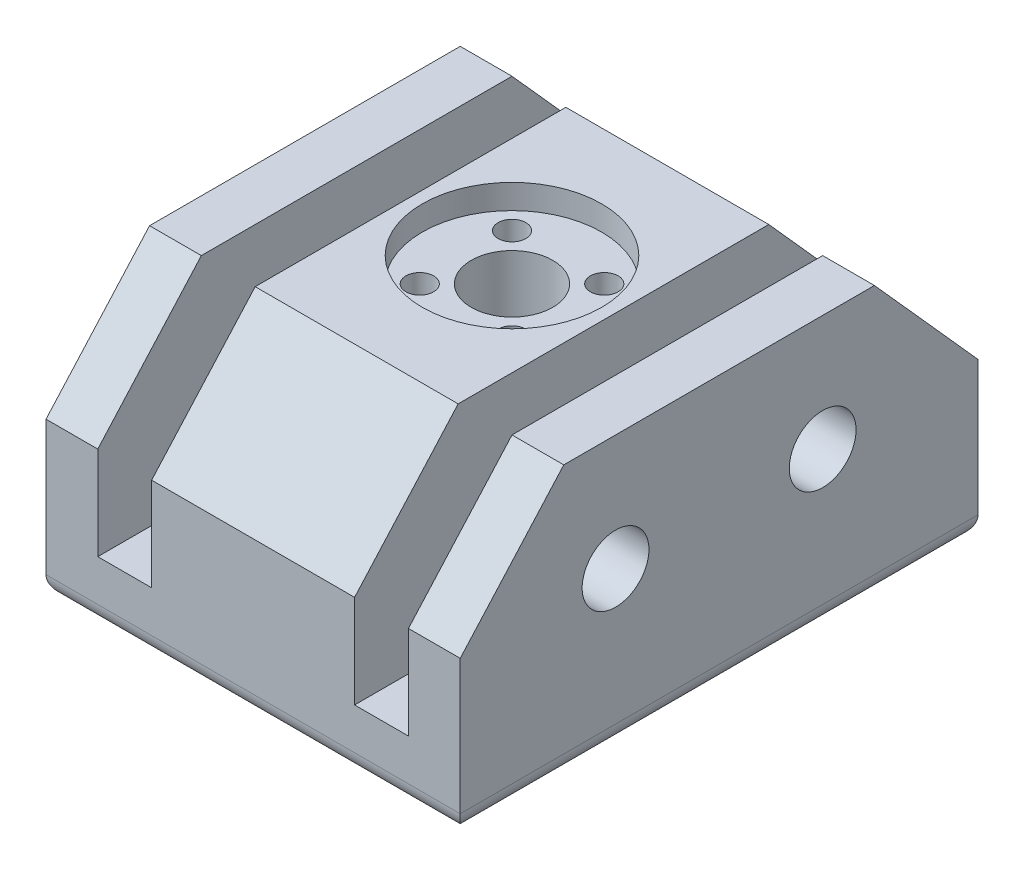
SolidWorks part; units mm, degrees
ref_plane "Front Plane" through (0, 0, 0) normal (0, 0, 1) x (1, 0, 0)
ref_plane "Top Plane" through (0, 0, 0) normal (0, 1, 0) x (1, 0, 0)
ref_plane "Right Plane" through (0, 0, 0) normal (1, 0, 0) x (0, 0, -1)
sketch "Sketch1" plane through (0, 0, 0) normal (1, 0, 0) x (0, 0, -1)
  line L1 (0, 0) -> (63.5, 0)
  line L2 (0, 0) -> (0, 6.35)
  line L3 (0, 6.35) -> (63.5, 6.35)
  line L4 (63.5, 0) -> (63.5, 6.35)
  dimension "D1" = 6.35
  dimension "D2" = 63.5
extrude "Boss-Extrude1" add sketch "Sketch1" against normal blind 50.8
sketch "Sketch2" plane through (0, 0, 0) normal (1, 0, 0) x (0, 0, -1)
  line L0 (0, 6.35) -> (0, 19.05)
  line L1 (0, 19.05) -> (12.7, 33.249)
  line L2 (12.7, 33.249) -> (50.8, 33.249)
  line L3 (50.8, 33.249) -> (63.5, 19.05)
  line L4 (63.5, 19.05) -> (63.5, 6.35)
  line L5 (63.5, 6.35) -> (0, 6.35)
  point P7 (31.75, 33.249)
  point P10 (31.75, 6.35)
  dimension "D1" = 38.1
  dimension "D2" = 12.7
  dimension "D3" = 12.7
  dimension "D4" = 19.05
  dimension "D5" = 19.05
extrude "Boss-Extrude2" add sketch "Sketch2" against normal blind 50.8
sketch "Sketch10" plane through (0, 0, -63.5) normal (0, 0, -1) x (-1, 0, 0)
  line L1 (50.8, 33.249) -> (0, 33.249) construction
  line L3 (6.35, 7.62) -> (6.35, 33.249)
  line L4 (6.35, 33.249) -> (12.954, 33.249)
  line L5 (12.954, 7.62) -> (12.954, 33.249)
  line L6 (6.35, 7.62) -> (12.954, 7.62)
  line L8 (50.8, 0) -> (0, 0) construction
  point P11 (12.954, 7.62)
  dimension "D1" = 7.62
  dimension "D2" = 6.604
  dimension "D3" = 6.35
extrude "Cut-Extrude1" cut sketch "Sketch10" against normal through all
pattern_linear "LPattern3" count 2 spacing 31.496 along (-1, 0, 0) of "Cut-Extrude1"
sketch "Sketch11" plane through (0, 0, 0) normal (1, 0, 0) x (0, 0, -1)
  circle A0 centre (19.05, 19.05) radius 4.0957
  circle A1 centre (19.05, 19.05) radius 7.9375 construction
  circle A2 centre (44.45, 19.05) radius 4.0958
  circle A3 centre (44.45, 19.05) radius 7.9375 construction
  dimension "D1" = 8.1915
  dimension "D3" = 15.875
  dimension "D4" = 8.1915
  dimension "D6" = 15.875
  dimension "D2" = 6.35
  dimension "D5" = 6.35
extrude "Cut-Extrude2" cut sketch "Sketch11" against normal through all
sketch "Sketch14" plane through (0, 33.249, 0) normal (0, 1, 0) x (1, 0, 0)
  line L3 (-37.846, 12.7) -> (-37.846, 50.8) construction
  point P0 (-25.4, 31.75)
  point P4 (-37.846, 31.75)
  dimension "D1" = 12.446
sketch "Sketch17" plane through (0, 40.0201, -44.7438) normal (0, 0.6667, -0.7454) x (-1, 0, 0)
  line L0 (12.954, -28.1343) -> (12.954, -9.0843) construction
  line L1 (37.846, -9.0843) -> (12.954, -9.0843) construction
  point P0 (25.4, -18.6093)
  point P4 (12.954, -18.6093)
  point P7 (25.4, -9.0843)
sketch "Sketch18" plane through (0, 8.4667, 9.466) normal (0, 0.6667, 0.7454) x (1, 0, 0)
  line L0 (-12.954, 33.249) -> (-12.954, 14.199) construction
  line L1 (-37.846, 33.249) -> (-12.954, 33.249) construction
  point P0 (-25.4, 23.724)
  point P1 (-25.4, 23.724)
  point P4 (-12.954, 23.724)
  point P7 (-25.4, 33.249)
ref_plane "Plane2" through (0, 33.02, 0) normal (0, -1, 0) x (-1, 0, 0)
fillet "Fillet1" radius 2.54 4 edges at (0, 0, -31.75) (-50.8, 0, -31.75) (-25.4, 0, 0) (-25.4, 0, -63.5)
sketch "Sketch21" plane through (0, 0, 0) normal (0, -1, 0) x (1, 0, 0)
  line L0 (-25.4, -63.5) -> (-25.4, 0) construction
  line L1 (-50.8, -63.5) -> (0, -63.5) construction
  line L2 (-50.8, 0) -> (0, 0) construction
  line L3 (-50.8, -31.75) -> (0, -31.75) construction
  line L4 (-50.8, 0) -> (-50.8, -63.5) construction
  line L5 (0, 0) -> (0, -63.5) construction
  circle A0 centre (-31.0569, -37.4069) radius 1.7
  circle A1 centre (-31.0569, -26.0931) radius 1.7
  circle A2 centre (-19.7431, -26.0931) radius 1.7
  circle A3 centre (-19.7431, -37.4069) radius 1.7
  point P14 (-25.4, -31.75)
  point P24 (-25.4, -31.75)
  dimension "D1" = 3.4
  dimension "D2" = 8
  dimension "D4" = 4
sketch "Sketch22" plane through (0, 33.249, 0) normal (0, -1, 0) x (1, 0, 0)
  line L1 (-25.4, -63.5) -> (-25.4, 0) construction
  line L2 (-50.8, -63.5) -> (0, -63.5) construction
  line L3 (-50.8, 0) -> (0, 0) construction
  line L4 (0, -31.75) -> (-50.8, -31.75) construction
  line L6 (0, 0) -> (0, -63.5) construction
  line L7 (-50.8, 0) -> (-50.8, -63.5) construction
  circle A1 centre (-25.4, -31.75) radius 11
  dimension "D1" = 22
extrude "Cut-Extrude7" cut sketch "Sketch21" against normal up to next
extrude "Cut-Extrude8" cut sketch "Sketch22" along normal blind 3
sketch "Sketch24" plane through (0, 0, 0) normal (0, -1, 0) x (1, 0, 0)
  line L0 (-25.4, -63.5) -> (-25.4, 0) construction
  line L1 (-50.8, -63.5) -> (0, -63.5) construction
  line L2 (-50.8, 0) -> (0, 0) construction
  line L3 (0, -31.75) -> (-50.8, -31.75) construction
  line L4 (0, 0) -> (0, -63.5) construction
  line L5 (-50.8, 0) -> (-50.8, -63.5) construction
  circle A0 centre (-25.4, -31.75) radius 5
  dimension "D1" = 10
extrude "Cut-Extrude10" cut sketch "Sketch24" against normal through all
sketch "Sketch28" plane through (0, 0, 0) normal (0, -1, 0) x (1, 0, 0)
  circle A0 centre (-19.7431, -37.4069) radius 3.125
  circle A1 centre (-25.4, -31.75) radius 8 construction
  circle A2 centre (-31.0569, -37.4069) radius 3.125
  circle A3 centre (-31.0569, -26.0931) radius 3.125
  circle A4 centre (-19.7431, -26.0931) radius 3.125
  point P16 (-25.4, -31.75)
  dimension "D1" = 6.25
  dimension "D2" = 4
extrude "Cut-Extrude11" cut sketch "Sketch28" against normal blind 5
